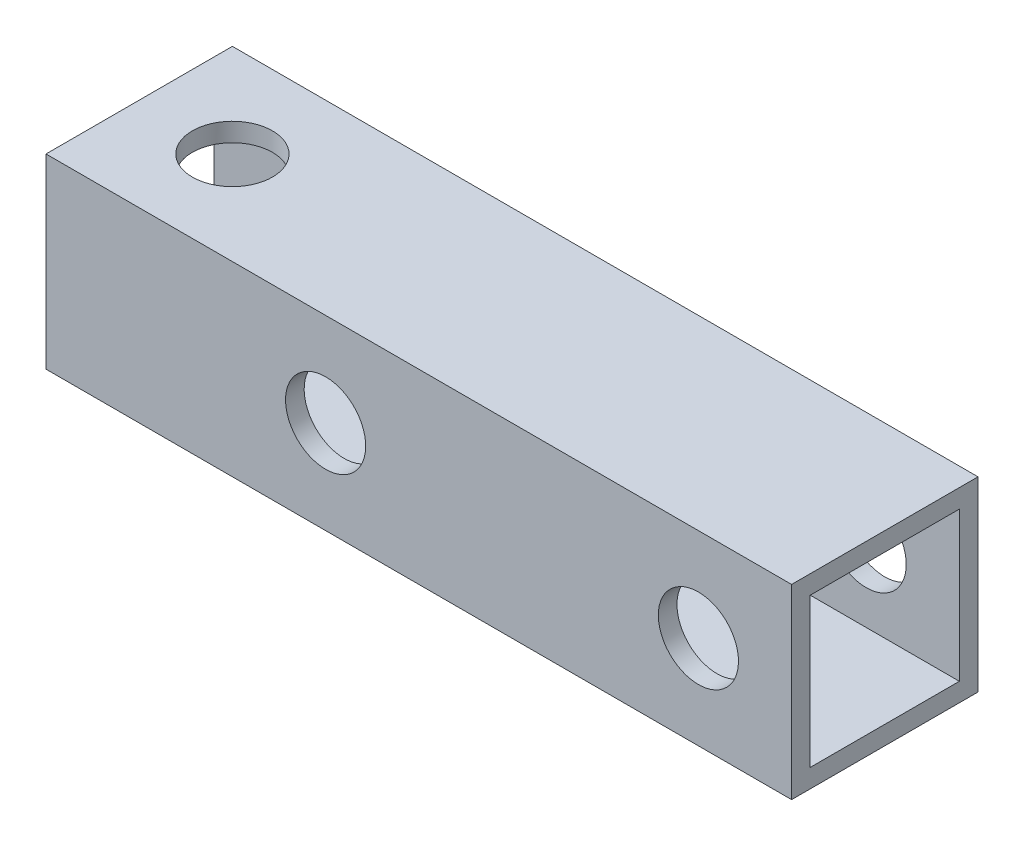
SolidWorks part; units mm, degrees
material "5052-H34"
ref_plane "正面" through (0, 0, 0) normal (0, 0, 1) x (1, 0, 0)
ref_plane "平面" through (0, 0, 0) normal (0, 1, 0) x (1, 0, 0)
ref_plane "右側面" through (0, 0, 0) normal (1, 0, 0) x (0, 0, -1)
sketch "ｽｹｯﾁ1" plane through (0, 0, 0) normal (1, 0, 0) x (0, 0, -1)
  line L1 (-5, 5) -> (5, 5)
  line L2 (-5, 5) -> (-5, -5)
  line L3 (-5, -5) -> (5, -5)
  line L4 (5, 5) -> (5, -5)
  line L5 (-5, 5) -> (5, -5) construction
  line L6 (-5, -5) -> (5, 5) construction
  point P0 (0, 0)
  dimension "D1" = 10
  dimension "D2" = 10
extrude "押し出し-薄板1" add sketch "ｽｹｯﾁ1" along normal blind 40 thin thin type one direction reverse wall 1
sketch "ｽｹｯﾁ2" plane through (0, 0, 5) normal (0, 0, 1) x (1, 0, 0)
  line L0 (0, 0) -> (35, 0) construction
  circle A0 centre (35, 0) radius 2.15
  circle A1 centre (15, 0) radius 2.15
  dimension "D3" = 4.3
  dimension "D1" = 15
  dimension "D2" = 20
extrude "ｶｯﾄ - 押し出し1" cut sketch "ｽｹｯﾁ2" against normal through all and the other way through all
sketch "ｽｹｯﾁ3" plane through (0, 5, 0) normal (0, 1, 0) x (1, 0, 0)
  line L0 (0, 0) -> (5, 0) construction
  circle A0 centre (5, 0) radius 2.15
  dimension "D2" = 4.3
  dimension "D1" = 5
extrude "ｶｯﾄ - 押し出し2" cut sketch "ｽｹｯﾁ3" against normal through all
